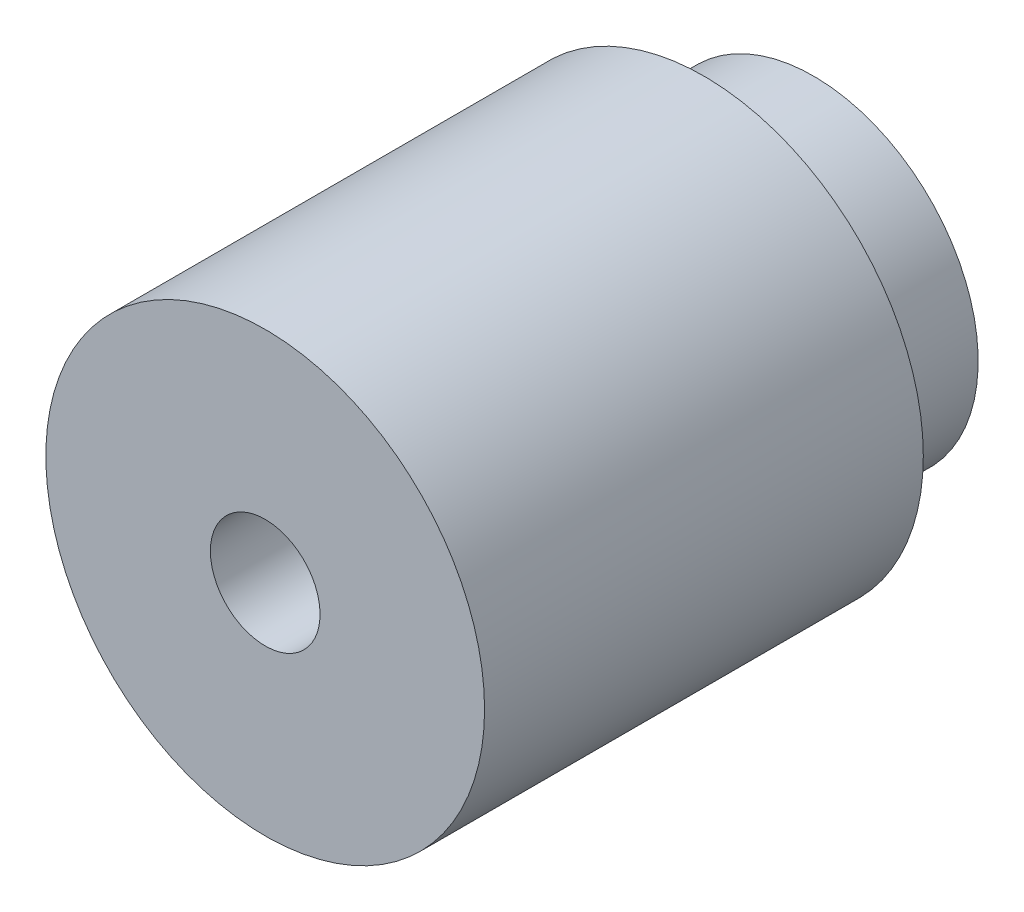
SolidWorks part; units mm, degrees
ref_plane "前视基准面" through (0, 0, 0) normal (0, 0, 1) x (1, 0, 0)
ref_plane "上视基准面" through (0, 0, 0) normal (0, 1, 0) x (1, 0, 0)
ref_plane "右视基准面" through (0, 0, 0) normal (1, 0, 0) x (0, 0, -1)
other "Configuration Table"
sketch "草图1" plane through (0, 0, 0) normal (0, 0, 1) x (1, 0, 0)
  circle A0 centre (0, 0) radius 20
extrude "凸台-拉伸1" add sketch "草图1" along normal blind 40
sketch "草图2" plane through (0, 0, 0) normal (0, 0, -1) x (-1, 0, 0)
  circle A0 centre (0, 0) radius 15
extrude "凸台-拉伸2" add sketch "草图2" along normal blind 10 separate body
sketch "草图3" plane through (0, 0, -10) normal (0, 0, -1) x (-1, 0, 0)
  circle A0 centre (0, 0) radius 5
extrude "切除-拉伸1" cut sketch "草图3" against normal blind 50
ref_plane "基准面1" through (0, 0, 20) normal (0, 0, 1) x (1, 0, 0)
sketch "草图6" plane through (0, 0, 20) normal (0, 0, 1) x (1, 0, 0)
  point P0 (0, 0)
sketch "草图7" plane through (0, 0, 20) normal (0, 0, 1) x (1, 0, 0)
  circle A0 centre (0, 0) radius 5 construction
  point P0 (5, 0)
  point P1 (-5, 0)
ref_axis "基准轴1" through (-25.9719, 0, 20) along (1, 0, 0)
sketch "草图8" plane through (0, 0, -10) normal (0, 0, -1) x (-1, 0, 0)
  line L1 (0, 0) -> (0, 15)
  circle A1 centre (0, 0) radius 15 construction
ref_point "点2"
ref_axis "基准轴2" through (0, 0, -10) along (0, 0, -1)
ref_axis "基准轴3" through (0, 0, -10) along (0, 1, 0)
